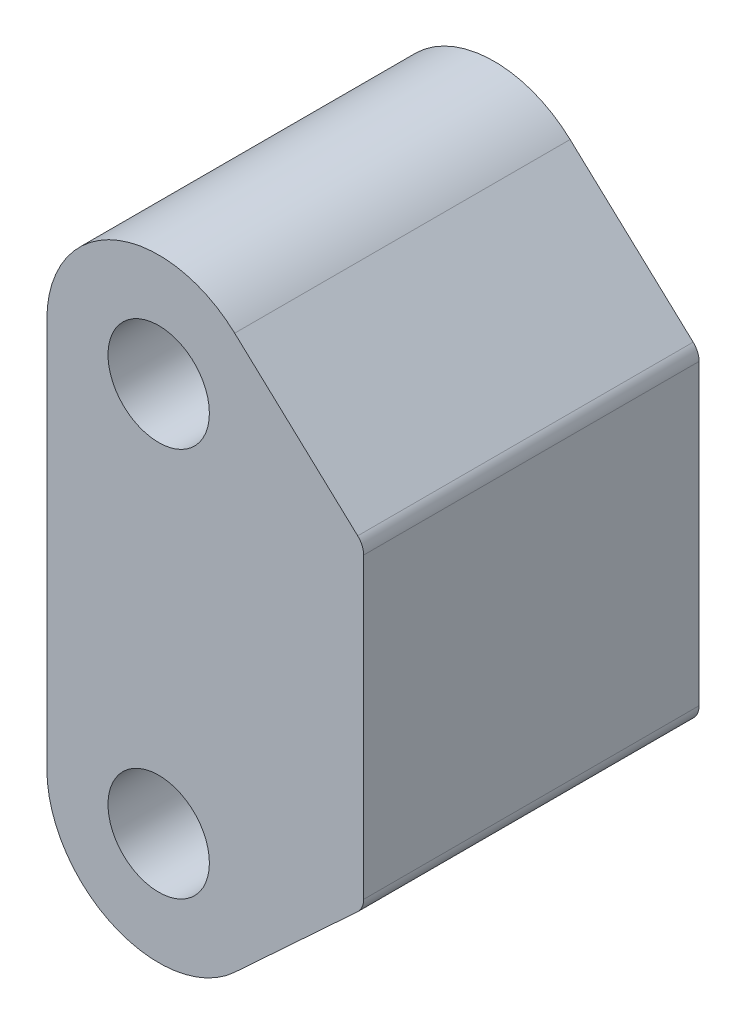
SolidWorks part; units mm, degrees
ref_plane "Front Plane" through (0, 0, 0) normal (0, 0, 1) x (1, 0, 0)
ref_plane "Top Plane" through (0, 0, 0) normal (0, 1, 0) x (1, 0, 0)
ref_plane "Right Plane" through (0, 0, 0) normal (1, 0, 0) x (0, 0, -1)
sketch "Sketch1" plane through (0, 0, 0) normal (0, 0, 1) x (1, 0, 0)
  line L0 (0, 0) -> (0, 16.5862) construction
  line L1 (-4.7625, 0) -> (-4.7625, 16.5862)
  line L2 (4.7625, 0) -> (4.7625, 16.5862)
  arc A0 (-4.7625, 0) -> (4.7625, 0) centre (0, 0) ccw
  arc A1 (4.7625, 16.5862) -> (-4.7625, 16.5862) centre (0, 16.5862) ccw
  point P3 (0, 8.2931)
  dimension "D1" = 4.7625
  dimension "D2" = 16.5862
extrude "Boss-Extrude1" add sketch "Sketch1" along normal blind 14.2875
sketch "Sketch2" plane through (0, 0, 14.2875) normal (0, 0, 1) x (1, 0, 0)
  line L1 (0, 20.2524) -> (-3.175, 18.4193)
  line L2 (-3.175, 18.4193) -> (-3.175, 14.7531)
  line L3 (-3.175, 14.7531) -> (0, 12.92)
  line L4 (0, 12.92) -> (3.175, 14.7531)
  line L5 (3.175, 14.7531) -> (3.175, 18.4193)
  line L6 (3.175, 18.4193) -> (0, 20.2524)
  line L7 (0, 3.6662) -> (-3.175, 1.8331)
  line L8 (-3.175, 1.8331) -> (-3.175, -1.8331)
  line L9 (-3.175, -1.8331) -> (0, -3.6662)
  line L10 (0, -3.6662) -> (3.175, -1.8331)
  line L11 (3.175, -1.8331) -> (3.175, 1.8331)
  line L12 (3.175, 1.8331) -> (0, 3.6662)
  circle A2 centre (0, 16.5862) radius 3.175 construction
  circle A3 centre (0, 0) radius 3.175 construction
  dimension "D1" = 6.35
extrude "Cut-Extrude1" [suppressed] cut sketch "Sketch2" against normal through all
sketch "Sketch3" plane through (0, 0, 14.2875) normal (0, 0, 1) x (1, 0, 0)
  line L0 (3.2365, 20.08) -> (8.4769, 15.2254)
  line L1 (8.7312, 14.6431) -> (8.7312, 1.9431)
  line L2 (8.4769, 1.3608) -> (3.2365, -3.4938)
  line L3 (4.7625, 0) -> (4.7625, 16.5862) construction
  line L4 (4.7625, 0) -> (4.7625, 16.5862)
  arc A0 (4.7625, 16.5862) -> (-4.7625, 16.5862) centre (0, 16.5862) ccw construction
  arc A1 (8.4769, 15.2254) -> (8.7312, 14.6431) centre (7.9375, 14.6431) cw
  arc A2 (8.7312, 1.9431) -> (8.4769, 1.3608) centre (7.9375, 1.9431) cw
  arc A3 (-4.7625, 0) -> (4.7625, 0) centre (0, 0) ccw construction
  arc A4 (3.2365, -3.4938) -> (4.7625, 0) centre (0, 0) ccw
  arc A5 (4.7625, 16.5862) -> (3.2365, 20.08) centre (0, 16.5862) ccw
  point P16 (4.7625, 8.2931)
  point P17 (8.7312, 8.2931)
  dimension "D3" = 0.7937
  dimension "D1" = 3.9688
  dimension "D2" = 12.7
extrude "Boss-Extrude2" add sketch "Sketch3" against normal up to surface (14.2875 mm away) up to face at (0, 8.2931, 0)
sketch "Sketch4" plane through (0, 0, 14.2875) normal (0, 0, 1) x (1, 0, 0)
  circle A0 centre (0, 16.5862) radius 2.159
  circle A1 centre (0, 0) radius 2.159
  dimension "D1" = 4.318
extrude "Cut-Extrude2" cut sketch "Sketch4" against normal through all
